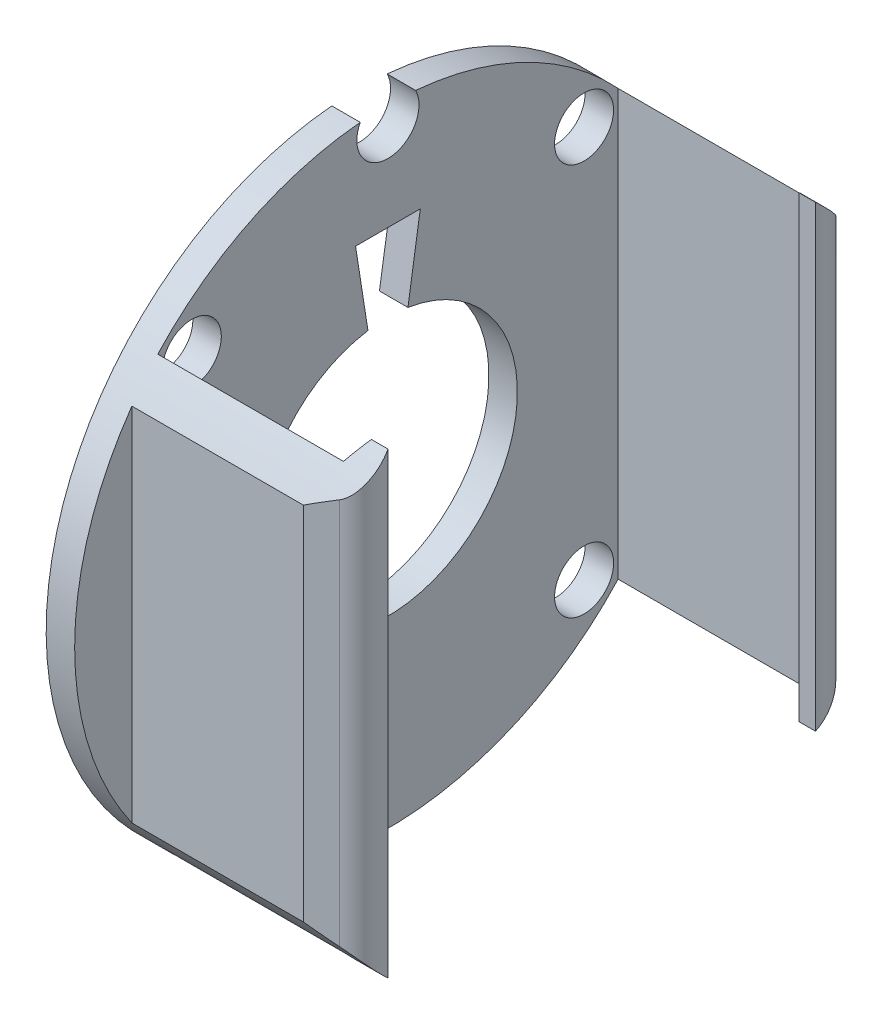
SolidWorks part; units mm, degrees
ref_plane "Front Plane" through (0, 0, 0) normal (0, 0, 1) x (1, 0, 0)
ref_plane "Top Plane" through (0, 0, 0) normal (0, 1, 0) x (1, 0, 0)
ref_plane "Right Plane" through (0, 0, 0) normal (1, 0, 0) x (0, 0, -1)
sketch "Sketch1" plane through (0, 0, 0) normal (1, 0, 0) x (0, 0, -1)
  circle A0 centre (0, 0) radius 60.5
  dimension "D1" = 121
extrude "Boss-Extrude1" add sketch "Sketch1" along normal blind 5.5 contours A0
sketch "Sketch2" plane through (5.5, 0, 0) normal (1, 0, 0) x (0, 0, -1)
  line L0 (0, 0) -> (0, 20.4757) construction
  line L1 (0, 0) -> (20.8293, 0) construction
  circle A0 centre (-37.875, 37.875) radius 5.7
  circle A1 centre (37.875, 37.875) radius 5.7
  circle A2 centre (37.875, -37.875) radius 5.7
  circle A3 centre (-37.875, -37.875) radius 5.7
  circle A4 centre (0, 0) radius 25
  point P17 (0, 25)
  dimension "D1" = 11.4
  dimension "D4" = 50
  dimension "D2" = 75.75
  dimension "D3" = 75.75
extrude "Cut-Extrude1" cut sketch "Sketch2" against normal through all
sketch "Sketch3" plane through (5.5, 0, 0) normal (1, 0, 0) x (0, 0, -1)
  line L0 (-49.45, 34.8561) -> (-49.45, -34.8561)
  line L1 (-44.45, -41.042) -> (44.45, -41.042) construction
  line L2 (-44.45, -41.042) -> (-44.45, 41.042)
  line L3 (-44.45, 41.042) -> (44.45, 41.042) construction
  line L4 (44.45, -41.042) -> (44.45, 41.042)
  line L5 (-44.45, -41.042) -> (44.45, 41.042) construction
  line L6 (-44.45, 41.042) -> (44.45, -41.042) construction
  line L7 (49.45, 34.8561) -> (49.45, -34.8561)
  circle A0 centre (0, 0) radius 60.5 construction
  circle A1 centre (0, 0) radius 60.5
  point P0 (0, 0)
  circle M13 centre (0, 0) radius 60.5
  dimension "D1" = 88.9
  dimension "D2" = 5
  dimension "D3" = 5
extrude "Boss-Extrude2" add sketch "Sketch3" along normal blind 38.1 contours L2 L0 M13 | L7 L4 M13
sketch "Sketch4" plane through (43.6, 0, 0) normal (1, 0, 0) x (0, 0, -1)
  line L0 (49.45, 34.8561) -> (49.45, -34.8561) construction
  line L1 (-49.45, 34.8561) -> (-49.45, -34.8561) construction
  line L2 (49.45, 34.8561) -> (49.45, -34.8561)
  line L3 (-49.45, 34.8561) -> (-49.45, -34.8561)
  line L4 (-41.275, 44.2337) -> (-41.275, -44.2337)
  line L5 (41.275, 44.2337) -> (41.275, -44.2337)
  line L6 (-44.45, -41.042) -> (-44.45, 41.042) construction
  line L7 (44.45, -41.042) -> (44.45, 41.042) construction
  circle A0 centre (0, 0) radius 60.5 construction
  circle A1 centre (0, 0) radius 60.5
  arc M4 (-49.45, -34.8561) -> (-44.45, -41.042) centre (0, 0) ccw
  line M5 (-44.45, -41.042) -> (-44.45, 41.042)
  arc M6 (-44.45, 41.042) -> (-49.45, 34.8561) centre (0, 0) ccw
  line M7 (-49.45, 34.8561) -> (-49.45, -34.8561)
  dimension "D1" = 3.175
  dimension "D2" = 3.175
extrude "Boss-Extrude3" add sketch "Sketch4" along normal blind 5 contours L4 A1 M5 | M7 M4 M5 M6 | L2 A1 L5
chamfer "Chamfer1" distance 10 angle 20 1 edges at (48.6, 0, 49.45)
chamfer "Chamfer2" distance 10 angle 20 1 edges at (48.6, 0, -49.45)
chamfer "Chamfer3" distance 5 angle 20 1 edges at (48.6, 0, 41.275)
chamfer "Chamfer4" distance 5 angle 20 1 edges at (48.6, 0, -41.275)
fillet "Fillet1" radius 5 2 edges at (48.4506, 0, -45.8647) (48.4506, 0, 45.8647)
chamfer "Chamfer5" distance 2.25 angle 55 1 edges at (43.6, 0, 44.45)
chamfer "Chamfer6" distance 2.25 angle 55 1 edges at (43.6, 0, -44.45)
sketch "Sketch5" plane through (5.5, 0, 0) normal (1, 0, 0) x (0, 0, -1)
  line L0 (0, 0) -> (-6.25, 40)
  line L1 (-6.25, 40) -> (6.25, 40)
  line L2 (6.25, 40) -> (0, 0)
  circle A0 centre (0, 57.5378) radius 6
  point P3 (0, 40)
  dimension "D3" = 12
  dimension "D1" = 12.5
  dimension "D2" = 40
extrude "Cut-Extrude2" cut sketch "Sketch5" against normal through all contours A0 | L2 L0 L1
